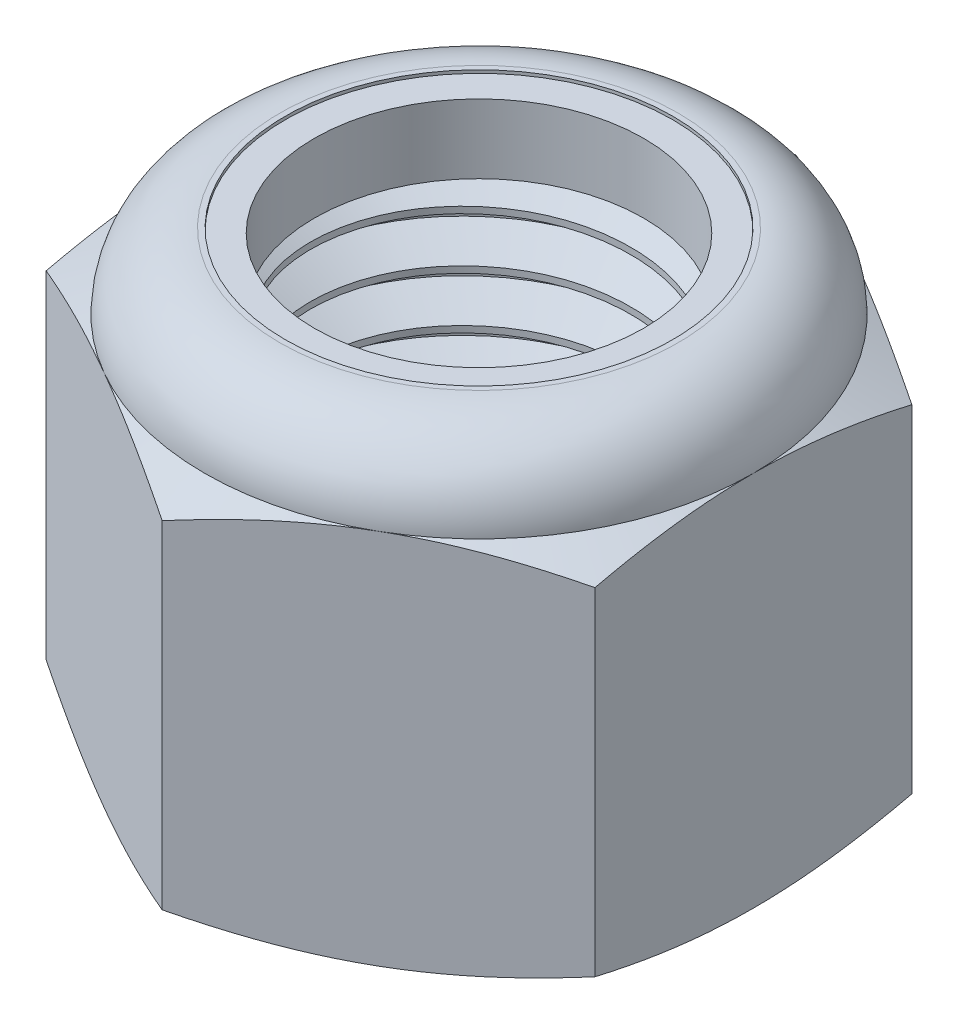
SolidWorks part; units mm, degrees
note: '?' marks a value the reader was unsure of.
ref_plane "Front" through (0, 0, 0) normal (0, 0, 1) x (1, 0, 0)
ref_plane "Top" through (0, 0, 0) normal (0, 1, 0) x (1, 0, 0)
ref_plane "Right" through (0, 0, 0) normal (1, 0, 0) x (0, 0, -1)
sketch "Sketch8" plane through (0, 0, 0) normal (1, 0, 0) x (0, 0, -1)
  line L0 (0, 0) -> (0, 22.225) construction
  line L1 (13.4937, 0) -> (-13.4937, 0) construction
  line L2 (-9.525, 22.225) -> (9.525, 22.225) construction
  line L3 (9.525, 22.225) -> (9.525, 19.685) construction
sketch "Sketch1" plane through (0, 0, 0) normal (0, 1, 0) x (1, 0, 0)
  line L1 (0, 15.5812) -> (-13.4937, 7.7906)
  line L2 (-13.4937, 7.7906) -> (-13.4937, -7.7906)
  line L3 (-13.4937, -7.7906) -> (0, -15.5812)
  line L4 (0, -15.5812) -> (13.4938, -7.7906)
  line L5 (13.4938, -7.7906) -> (13.4938, 7.7906)
  line L6 (13.4938, 7.7906) -> (0, 15.5812)
  circle A0 centre (0, 0) radius 13.4938 construction
  circle A1 centre (0, 0) radius 9.525
extrude "Extrude1" add sketch "Sketch1" along normal up to vertex (22.225 mm away) up to point (0, 22.225, 0)
sketch "Sketch5" plane through (0, 0, 0) normal (1, 0, 0) x (0, 0, -1)
  line L0 (0, 0) -> (13.4937, 0)
  line L1 (13.4937, 0) -> (15.5812, 0.9734)
  line L2 (15.5812, 0.9734) -> (15.5812, 17.5474)
  line L3 (15.5812, 17.5474) -> (13.4937, 18.5208)
  line L4 (9.7896, 22.225) -> (9.7896, 23.495)
  line L5 (9.7896, 23.495) -> (16.8512, 23.495)
  line L6 (16.8512, 23.495) -> (16.8512, -1.27)
  line L7 (16.8512, -1.27) -> (0, -1.27)
  line L8 (0, -1.27) -> (0, 0)
  line L9 (13.4937, 18.5208) -> (13.4937, 0) construction
  line L12 (15.5812, 22.225) -> (15.5812, 0) construction
  line L13 (15.5812, 11.1125) -> (16.8512, 11.1125) construction
  line L15 (0, 0) -> (0, 23.495) construction
  line L18 (13.4937, 0) -> (-13.4937, 0) construction
  line L19 (7.7906, 22.225) -> (15.5812, 22.225) construction
  line L20 (0, 23.495) -> (9.7896, 23.495) construction
  line L21 (7.7906, 0) -> (15.5812, 0) construction
  arc A0 (13.4937, 18.5208) -> (9.7896, 22.225) centre (9.7896, 18.5208) ccw
  dimension "D1" = 25
  dimension "D2" = 1.27
  dimension "D4" = 3.7042
revolve "Cut-Revolve3" cut sketch "Sketch5" angle 360 about L15
sketch "Sketch4" plane through (0, 0, 0) normal (1, 0, 0) x (0, 0, -1)
  line L0 (0, 18.5208) -> (10.4775, 18.5208)
  line L1 (10.4775, 18.5208) -> (0, 13.6351)
  line L3 (0, 4.8857) -> (10.4775, 0)
  line L4 (10.4775, 0) -> (0, 0)
  line L5 (0, 0) -> (0, 18.5208) construction
  line L10 (0, 0) -> (0, 22.225) construction
  line L11 (0, 4.8857) -> (0, 0)
  line L12 (0, 18.5208) -> (0, 13.6351)
  line L13 (11.6859, 18.5208) -> (0, 18.5208) construction
  dimension "D1" = 25
  dimension "D2" = 20.955
sketch "Sketch6" plane through (0, 0, 0) normal (1, 0, 0) x (0, 0, -1)
  line L0 (0, 18.5208) -> (13.3414, 18.5208)
  line L1 (9.7896, 22.0726) -> (4.8948, 22.0726)
  line L2 (0, 23.495) -> (0, 18.5208)
  line L3 (4.8948, 23.495) -> (0, 23.495)
  line L4 (0, 23.495) -> (9.7896, 23.495) construction
  line L5 (0, 0) -> (0, 23.495) construction
  line L6 (0, 23.495) -> (0, 0) construction
  line L7 (4.8948, 22.0726) -> (4.8948, 23.495)
  line L8 (9.7896, 22.225) -> (9.7896, 22.0726) construction
  line L9 (4.8948, 22.0726) -> (0, 22.0726) construction
  line L10 (0, 22.0726) -> (0, 13.6351) construction
  arc A0 (13.3414, 18.5208) -> (9.7896, 22.0726) centre (9.7896, 18.5208) ccw
  arc A1 (13.4937, 18.5208) -> (9.7896, 22.225) centre (9.7896, 18.5208) ccw construction
  dimension "D1" = 0.1524
revolve "Cut-Revolve4" cut sketch "Sketch6" angle 360 about L6
revolve "Cut-Revolve2" cut sketch "Sketch4" angle 360 about L5
sketch "Sketch7" plane through (0, 0, 0) normal (1, 0, 0) x (0, 0, -1)
  line L0 (8.0962, 18.597) -> (13.2643, 18.597)
  line L1 (9.7896, 21.9964) -> (8.0962, 21.9964)
  line L2 (8.0962, 21.9964) -> (8.0962, 18.597)
  line L3 (8.0962, 18.597) -> (0, 18.597) construction
  line L4 (0, 18.597) -> (0, 21.9964) construction
  line L5 (0, 21.9964) -> (8.0962, 21.9964) construction
  line L6 (8.0962, 18.597) -> (8.0962, 18.5208) construction
  line L7 (0, 18.5208) -> (13.3414, 18.5208) construction
  line L8 (9.7896, 21.9964) -> (9.7896, 22.0726) construction
  arc A0 (13.2643, 18.597) -> (9.7896, 21.9964) centre (9.7896, 18.5208) ccw
  arc A2 (13.3414, 18.5208) -> (9.7896, 22.0726) centre (9.7896, 18.5208) ccw construction
  dimension "D1" = 0.0762
  dimension "D2" = 16.1925
revolve "Revolve2" add sketch "Sketch7" angle 360 about L4
sketch "Sketch2" plane through (0, 0, 0) normal (1, 0, 0) x (0, 0, -1)
  line L0 (-9.525, 0) -> (-9.525, 18.5208) construction
  line L1 (0, 0) -> (9.525, 0)
  line L2 (0, 0) -> (0, 18.5208)
  line L3 (0, 18.5208) -> (9.525, 18.5208)
  line L4 (9.525, 0) -> (9.525, 18.5208)
  line L6 (11.6859, 18.5208) -> (13.4937, 18.5208) construction
  line L7 (0, -9.525) -> (0, 0) construction
revolve "Revolve1" add sketch "Sketch2" angle 360 about L7
sketch "Sketch9" plane through (0, 0, 0) normal (1, 0, 0) x (0, 0, -1)
  line L0 (9.8, 20.9021) -> (9.8, 18.3621) construction
  line L1 (9.8, 18.3621) -> (7.6003, 19.6321) construction
  line L2 (7.6003, 19.6321) -> (9.8, 20.9021) construction
  line L3 (7.8752, 19.7908) -> (7.8752, 19.4733) construction
  line L4 (9.525, 20.7433) -> (9.525, 18.5208) construction
  line L5 (7.6003, 19.6321) -> (7.8752, 19.6321) construction
  line L6 (9.525, 19.6321) -> (9.8, 19.6321) construction
  line L7 (9.6625, 19.6321) -> (9.6625, 20.8227) construction
  line L8 (9.8, 18.3621) -> (9.6625, 20.8227)
  line L9 (9.6625, 20.8227) -> (7.8752, 19.7908)
  line L10 (7.8752, 19.7908) -> (7.8752, 19.4733)
  line L11 (7.8752, 19.4733) -> (9.8, 18.3621)
  dimension "D1" = 2.54
  dimension "D2" = 0.3175
sketch "Sketch10" plane through (0, 18.5208, 0) normal (0, 1, 0) x (1, 0, 0)
  circle A1 centre (0, 0) radius 9.525
  circle A2 centre (0, 0) radius 9.525
  dimension "D1" = 0
curve "Helix/Spiral1" pitch 2.54 height 24.765 turns 9.75
sweep "Cut-Sweep1" cut profiles "Sketch9" path "Helix/Spiral1" align with end faces yes
sketch "Sketch11" plane through (0, 0, 0) normal (1, 0, 0) x (0, 0, -1)
  line L0 (0, 0) -> (0, 22.225) construction
  line L1 (13.4937, 0) -> (-13.4937, 0) construction
  line L4 (0, 22.225) -> (0, 0) construction
  line L5 (0, 11.1125) -> (9.525, 11.1125) construction
  line L6 (0, 0) -> (10.4775, 0)
  line L7 (0, 4.8857) -> (0, 0)
  line L8 (10.4775, 0) -> (0, 4.8857)
  dimension "D1" = 20.955
  dimension "D2" = 25
revolve "Revolve3" add sketch "Sketch11" angle 360 about L4
sketch "Sketch12" plane through (0, 0, 0) normal (1, 0, 0) x (0, 0, -1)
  line L0 (10.4775, 18.5208) -> (0, 18.5208)
  line L1 (0, 18.5208) -> (0, 0)
  line L2 (0, 0) -> (10.4775, 0)
  line L3 (13.4937, 0) -> (-13.4937, 0) construction
  line L4 (10.4775, 0) -> (10.4775, 18.5208)
  line L5 (-10.4775, 0) -> (10.4775, 0) construction
revolve "Revolve4" add sketch "Sketch12" angle 360 about L0
combine bodies "Combine1" operation type subtract main body 136 bodies to subtract 133
ref_plane "Contact Plane 1" through (0, 0, 0) normal (0, -1, 0) x (1, 0, 0)
ref_axis "Center Axis 1" through (0, -2.1015, 0) along (0, 1, 0)?
equation "\"D4@Sketch5\"=\"Height@Sketch8\"/6"
equation "\"D1@Sketch9\"=\"Thread Pitch@Sketch8\""
equation "\"D2@Sketch9\"=\"Thread Pitch@Sketch8\"/8"
equation "\"D4@Helix/Spiral1\"=\"Thread Pitch@Sketch8\""
equation "\"D3@Helix/Spiral1\"=\"Thread Pitch@Sketch8\"+\"Height@Sketch8\""
equation "\"D2@Sketch4\"=\"Thread Dia@Sketch8\"*1.1"
equation "\"D1@Sketch11\"=\"Thread Dia@Sketch8\"*1.1"
equation "\"D2@Sketch7\"=\"Thread Dia@Sketch8\"*.85"
